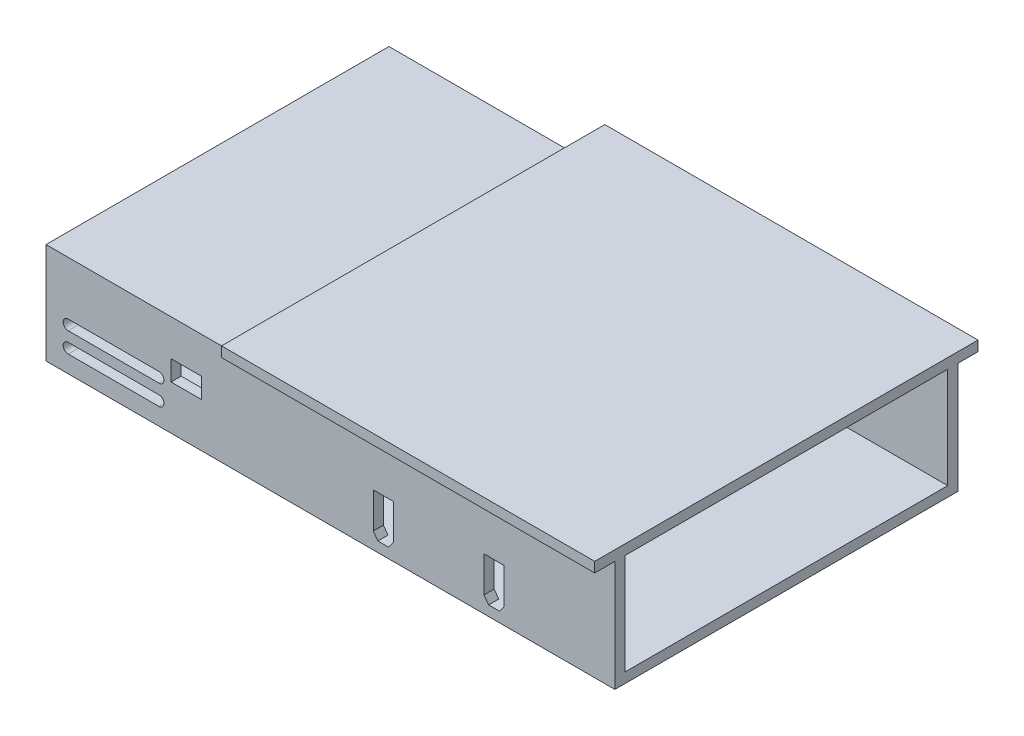
SolidWorks part; units mm, degrees
material "ABS"
ref_plane "Front Plane" through (0, 0, 0) normal (0, 0, 1) x (1, 0, 0)
ref_plane "Top Plane" through (0, 0, 0) normal (0, 1, 0) x (1, 0, 0)
ref_plane "Right Plane" through (0, 0, 0) normal (1, 0, 0) x (0, 0, -1)
sketch "Sketch1" plane through (0, 0, 0) normal (0, 1, 0) x (1, 0, 0)
  line L1 (0, 0) -> (282, 0)
  line L2 (0, 0) -> (0, 170)
  line L3 (0, 170) -> (282, 170)
  line L4 (282, 0) -> (282, 170)
  dimension "D1" = 170
  dimension "D2" = 282
extrude "Boss-Extrude1" add sketch "Sketch1" along normal blind 60
sketch "Sketch7" plane through (0, 0, 0) normal (0, -1, 0) x (1, 0, 0)
  line L0 (0, -170) -> (0, 0) construction
  line L3 (11, -37.5) -> (11, -132.5) construction
  line L4 (13.5, -37.5) -> (13.5, -132.5)
  line L5 (8.5, -37.5) -> (8.5, -132.5)
  line L6 (56, -37.5) -> (56, -132.5) construction
  line L7 (58.5, -37.5) -> (58.5, -132.5)
  line L8 (53.5, -37.5) -> (53.5, -132.5)
  line L9 (26, -37.5) -> (26, -132.5) construction
  line L10 (28.5, -37.5) -> (28.5, -132.5)
  line L11 (23.5, -37.5) -> (23.5, -132.5)
  line L12 (41, -37.5) -> (41, -132.5) construction
  line L13 (43.5, -37.5) -> (43.5, -132.5)
  line L14 (38.5, -37.5) -> (38.5, -132.5)
  line L15 (0, -85) -> (282, -85) construction
  line L16 (282, 0) -> (282, -170) construction
  arc A2 (13.5, -37.5) -> (8.5, -37.5) centre (11, -37.5) ccw
  arc A3 (8.5, -132.5) -> (13.5, -132.5) centre (11, -132.5) ccw
  arc A4 (58.5, -37.5) -> (53.5, -37.5) centre (56, -37.5) ccw
  arc A5 (53.5, -132.5) -> (58.5, -132.5) centre (56, -132.5) ccw
  arc A6 (28.5, -37.5) -> (23.5, -37.5) centre (26, -37.5) ccw
  arc A7 (23.5, -132.5) -> (28.5, -132.5) centre (26, -132.5) ccw
  arc A8 (43.5, -37.5) -> (38.5, -37.5) centre (41, -37.5) ccw
  arc A9 (38.5, -132.5) -> (43.5, -132.5) centre (41, -132.5) ccw
  point P9 (11, -85)
  point P16 (56, -85)
  point P23 (26, -85)
  point P30 (41, -85)
  point P35 (11, -35)
  point P36 (11, -135)
  point P42 (26, -35)
  point P43 (26, -135)
  point P44 (41, -35)
  point P45 (41, -135)
  point P46 (56, -35)
  point P47 (56, -135)
  dimension "D1" = 8.5
  dimension "D6" = 100
  dimension "D7" = 100
  dimension "D9" = 100
  dimension "D2" = 5
  dimension "D3" = 5
  dimension "D4" = 5
  dimension "D5" = 5
  dimension "D8" = 100
  dimension "D10" = 15
  dimension "D11" = 15
  dimension "D12" = 15
extrude "Cut-Extrude4" cut sketch "Sketch7" against normal blind 5
sketch "Sketch8" plane through (282, 0, 0) normal (1, 0, 0) x (0, 0, -1)
  line L0 (0, 60) -> (0, 0) construction
  line L1 (5, 55) -> (165, 55)
  line L2 (5, 55) -> (5, 5)
  line L3 (5, 5) -> (165, 5)
  line L4 (165, 55) -> (165, 5)
  line L5 (170, 60) -> (170, 0) construction
  line L6 (0, 0) -> (170, 0) construction
  line L7 (0, 60) -> (170, 60) construction
  dimension "D1" = 5
  dimension "D2" = 5
  dimension "D3" = 5
  dimension "D4" = 5
extrude "Cut-Extrude5" cut sketch "Sketch8" against normal blind 279
sketch "Sketch9" plane through (0, 0, 0) normal (0, 0, 1) x (1, 0, 0)
  line L0 (217.15, 25.8) -> (227.05, 25.8)
  line L1 (162.25, 25.8) -> (172.15, 25.8)
  line L2 (162.25, 25.8) -> (162.25, 8.15)
  line L3 (164.5, 5) -> (169.9, 5)
  line L4 (172.15, 25.8) -> (172.15, 8.15)
  line L5 (217.15, 25.8) -> (217.15, 8.15)
  line L6 (219.4, 5) -> (224.8, 5)
  line L7 (227.05, 25.8) -> (227.05, 8.15)
  line L8 (282, 60) -> (282, 0) construction
  line L9 (0, 0) -> (282, 0) construction
  line L10 (162.25, 8.15) -> (164.5, 5)
  line L11 (169.9, 5) -> (172.15, 8.15)
  line L12 (217.15, 8.15) -> (219.4, 5)
  line L13 (227.05, 8.15) -> (224.8, 5)
  dimension "D1" = 9.9
  dimension "D2" = 3.15
  dimension "D3" = 54.95
  dimension "D4" = 45
  dimension "D5" = 9.9
  dimension "D6" = 20.8
  dimension "D7" = 5
  dimension "D8" = 2.25
  dimension "D9" = 20.8
  dimension "D10" = 2.25
  dimension "D11" = 3.15
  dimension "D12" = 3.15
  dimension "D13" = 3.15
  dimension "D14" = 2.25
  dimension "D15" = 2.25
  dimension "D16" = 25.8
extrude "Cut-Extrude6" cut sketch "Sketch9" against normal blind 5
sketch "Sketch10" plane through (0, 0, 0) normal (-1, 0, 0) x (0, 0, 1)
  line L0 (-170, 20) -> (0, 20) construction
  line L1 (-170, 60) -> (-170, 0) construction
  line L2 (0, 60) -> (0, 0) construction
  line L3 (-170, 0) -> (0, 0) construction
  circle A0 centre (-129.2022, 20) radius 5
  circle A1 centre (-114.2022, 20) radius 5
  circle A2 centre (-99.2022, 20) radius 5
  circle A3 centre (-43.3901, 20) radius 5
  circle A4 centre (-58.3901, 20) radius 5
  circle A5 centre (-73.3901, 20) radius 5
  dimension "D1" = 15
  dimension "D3" = 10
  dimension "D4" = 10
  dimension "D5" = 10
  dimension "D6" = 10
  dimension "D7" = 10
  dimension "D8" = 10
  dimension "D2" = 15
  dimension "D9" = 15
  dimension "D10" = 15
  dimension "D11" = 20
extrude "Cut-Extrude7" cut sketch "Sketch10" against normal blind 5
sketch "Sketch11" plane through (0, 0, 0) normal (0, 0, 1) x (1, 0, 0)
  line L0 (11, 11) -> (56, 11) construction
  line L1 (11, 13.5) -> (56, 13.5)
  line L2 (11, 8.5) -> (56, 8.5)
  line L3 (11, 21) -> (56, 21) construction
  line L4 (11, 23.5) -> (56, 23.5)
  line L5 (11, 18.5) -> (56, 18.5)
  line L9 (0, 60) -> (0, 0) construction
  line L10 (0, 0) -> (282, 0) construction
  arc A0 (11, 13.5) -> (11, 8.5) centre (11, 11) ccw
  arc A1 (56, 8.5) -> (56, 13.5) centre (56, 11) ccw
  arc A2 (11, 23.5) -> (11, 18.5) centre (11, 21) ccw
  arc A3 (56, 18.5) -> (56, 23.5) centre (56, 21) ccw
  point P2 (33.5, 11)
  point P9 (33.5, 21)
  point P21 (8.5, 11)
  point P24 (33.5, 8.5)
  point P27 (58.5, 11)
  point P28 (58.5, 21)
  point P29 (8.5, 21)
  dimension "D1" = 8.5
  dimension "D2" = 8.5
  dimension "D3" = 5
  dimension "D4" = 5
  dimension "D6" = 50
  dimension "D7" = 50
  dimension "D9" = 5
sketch "Sketch12" plane through (0, 0, -170) normal (0, 0, -1) x (-1, 0, 0)
  line L0 (-56, 11) -> (-11, 11) construction
  line L1 (-56, 13.5) -> (-11, 13.5)
  line L2 (-56, 8.5) -> (-11, 8.5)
  line L3 (-56, 21) -> (-11, 21) construction
  line L4 (-56, 23.5) -> (-11, 23.5)
  line L5 (-56, 18.5) -> (-11, 18.5)
  line L9 (-282, 0) -> (0, 0) construction
  line L10 (0, 60) -> (0, 0) construction
  arc A0 (-56, 13.5) -> (-56, 8.5) centre (-56, 11) ccw
  arc A1 (-11, 8.5) -> (-11, 13.5) centre (-11, 11) ccw
  arc A2 (-56, 23.5) -> (-56, 18.5) centre (-56, 21) ccw
  arc A3 (-11, 18.5) -> (-11, 23.5) centre (-11, 21) ccw
  point P2 (-33.5, 11)
  point P12 (-33.5, 21)
  point P26 (-8.5, 11)
  point P27 (-58.5, 11)
  point P28 (-8.5, 21)
  point P29 (-58.5, 21)
  dimension "D1" = 8.5
  dimension "D2" = 5
  dimension "D3" = 5
  dimension "D5" = 50
  dimension "D6" = 50
  dimension "D8" = 8.5
  dimension "D9" = 5
extrude "Cut-Extrude8" cut sketch "Sketch11" against normal blind 5
extrude "Cut-Extrude9" cut sketch "Sketch12" against normal blind 5
sketch "Sketch14" plane through (0, 0, 0) normal (0, 0, 1) x (1, 0, 0)
  line L0 (282, 60) -> (282, 0) construction
  line L1 (282, 60) -> (97, 60)
  line L2 (282, 60) -> (282, 55)
  line L3 (282, 55) -> (97, 55)
  line L4 (97, 60) -> (97, 55)
  line L5 (0, 60) -> (282, 60) construction
  dimension "D1" = 5
  dimension "D2" = 185
extrude "Boss-Extrude2" add sketch "Sketch14" along normal blind 10
sketch "Sketch15" plane through (0, 0, -170) normal (0, 0, -1) x (-1, 0, 0)
  line L1 (-282, 60) -> (-97, 60)
  line L2 (-282, 60) -> (-282, 55)
  line L3 (-282, 55) -> (-97, 55)
  line L4 (-97, 60) -> (-97, 55)
  dimension "D1" = 5
  dimension "D2" = 185
extrude "Boss-Extrude3" add sketch "Sketch15" along normal blind 10
sketch "Sketch16" plane through (0, 0, 0) normal (0, 0, 1) x (1, 0, 0)
  line L0 (97, 60) -> (97, 55) construction
  line L1 (0, 60) -> (97, 60)
  line L2 (0, 60) -> (0, 50)
  line L3 (0, 50) -> (97, 50)
  line L4 (97, 60) -> (97, 50)
  dimension "D2" = 10
extrude "Cut-Extrude10" cut sketch "Sketch16" against normal blind 170
sketch "Sketch17" plane through (0, 0, -165) normal (0, 0, 1) x (1, 0, 0)
  line L1 (3, 50) -> (97, 50)
  line L2 (3, 50) -> (3, 45)
  line L5 (97, 55) -> (282, 55) construction
  line L7 (97, 50) -> (97, 55)
  line L8 (97, 55) -> (102, 55)
  line L9 (102, 45) -> (102, 55)
  line L11 (102, 45) -> (3, 45)
  line L12 (97, 55) -> (97, 50) construction
  dimension "D1" = 5
  dimension "D2" = 5
extrude "Boss-Extrude4" add sketch "Sketch17" along normal blind 160
sketch "Sketch18" plane through (0, 0, 0) normal (0, 0, 1) x (1, 0, 0)
  line L1 (62, 32) -> (77, 32)
  line L2 (62, 32) -> (62, 22)
  line L3 (62, 22) -> (77, 22)
  line L4 (77, 32) -> (77, 22)
  line L5 (97, 50) -> (97, 55) construction
  line L8 (0, 50) -> (97, 50) construction
  dimension "D1" = 15
  dimension "D2" = 10
  dimension "D3" = 18
  dimension "D4" = 20
extrude "Cut-Extrude11" cut sketch "Sketch18" against normal through all
